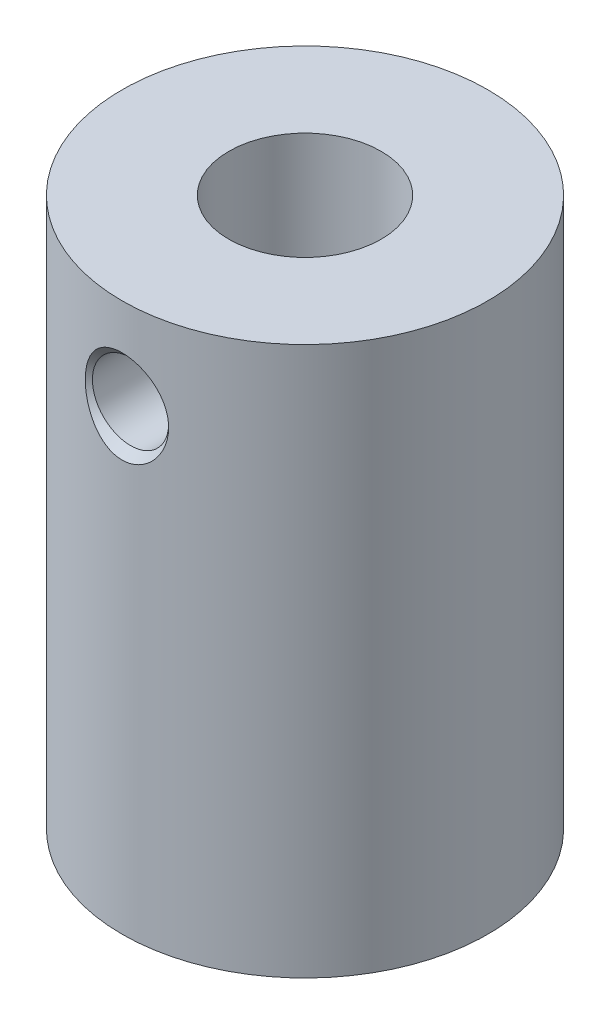
SolidWorks part; units mm, degrees
ref_plane "Front Plane" through (0, 0, 0) normal (0, 0, 1) x (1, 0, 0)
ref_plane "Top Plane" through (0, 0, 0) normal (0, 1, 0) x (1, 0, 0)
ref_plane "Right Plane" through (0, 0, 0) normal (1, 0, 0) x (0, 0, -1)
sketch "Sketch1" plane through (0, 0, 0) normal (0, 1, 0) x (1, 0, 0)
  circle A0 centre (0, 0) radius 6
  circle A1 centre (0, 0) radius 2.5
  dimension "D1" = 12
  dimension "D2" = 5
extrude "Boss-Extrude1" add sketch "Sketch1" along normal blind 18
cosmetic thread "Hole Thread3" parameters "D1"=11.475, "D2"=6
cosmetic thread "Hole Thread4" parameters "D1"=29.475, "D2"=6
ref_plane "Plane2" through (0, 0, 6) normal (0, 0, 1) x (1, 0, 0)
hole_wizard "M3 Tapped Hole1" positions "Sketch9" profile "Sketch10" tap size "M3" standard "ISO" end condition up to next
sketch "Sketch9" plane through (0, 0, 6) normal (0, 0, 1) x (1, 0, 0)
  line L0 (0, 0) -> (0, 14.0249) construction
  line L2 (6, 18) -> (-6, 18) construction
  point P1 (0, 15)
  dimension "D1" = 3
sketch "Sketch10" plane through (0, 15, 6) normal (1, 0, 0) x (0, -1, 0)
  line L0 (0, 0) -> (0, 3.5)
  line L1 (0, 3.5) -> (1.525, 3.5)
  line L2 (1.25, 3.225) -> (1.25, 0.275)
  line L3 (1.25, 0.275) -> (1.525, 0)
  line L5 (1.525, 0) -> (0, 0)
  line L6 (-1.25, 0.275) -> (-1.525, 0) construction
  line L7 (1.525, 3.5) -> (1.25, 3.225)
  line L8 (-1.525, 3.5) -> (-1.25, 3.225) construction
  line L11 (0, -6.35) -> (0, 107.95) construction
  dimension "Thru Tap Drill Dia." = 2.5
  dimension "Thru Tap Drill Depth" = 3.5
  dimension "Near C'Sink Dia." = 3.05
  dimension "Near C'Sink Angle" = 90
  dimension "Far C'Sink Dia." = 3.05
  dimension "Far C'Sink Angle" = 90
cosmetic thread "Hole Thread2" parameters "D2"=3
hole_wizard "M6 Tapped Hole1" positions "Sketch12" profile "Sketch11" tap size "M6" standard "ISO"
sketch "Sketch12" plane through (0, 0, 0) normal (0, 1, 0) x (1, 0, 0)
  point P0 (0, 0)
sketch "Sketch11" plane through (0, 0, 0) normal (1, 0, 0) x (0, 0, -1)
  line L0 (0, 0) -> (0, 11.5022)
  line L1 (0, 11.5022) -> (2.5, 10)
  line L2 (2.5, 10) -> (2.5, 0.525)
  line L3 (2.5, 0.525) -> (3.025, 0)
  line L5 (3.025, 0) -> (0, 0)
  line L6 (-2.5, 0.525) -> (-3.025, 0) construction
  line L10 (0, 11.5022) -> (-2.5, 10) construction
  line L11 (0, -6.35) -> (0, 107.95) construction
  dimension "Tap Drill Dia." = 5
  dimension "Tap Drill Depth" = 10
  dimension "Near C'Sink Dia." = 6.05
  dimension "Near C'Sink Angle" = 90
  dimension "Drill Angle" = 118
